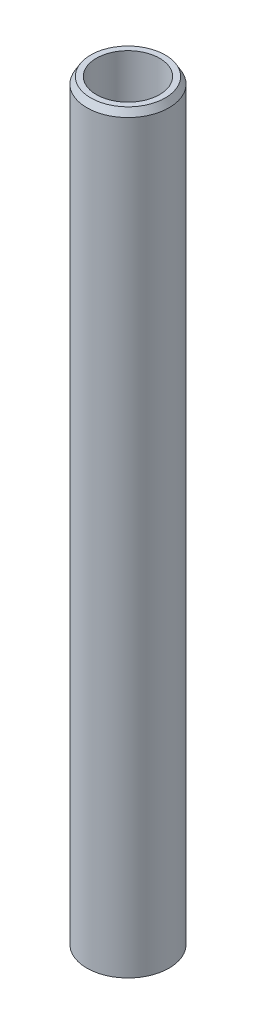
SolidWorks part; units mm, degrees
ref_plane "Front Plane" through (0, 0, 0) normal (0, 0, 1) x (1, 0, 0)
ref_plane "Top Plane" through (0, 0, 0) normal (0, 1, 0) x (1, 0, 0)
ref_plane "Right Plane" through (0, 0, 0) normal (1, 0, 0) x (0, 0, -1)
sketch "Sketch1" plane through (0, 0, 0) normal (0, 1, 0) x (1, 0, 0)
  circle A0 centre (0, 0) radius 17.5
  dimension "SHAFT_OD" = 35
extrude "Boss-Extrude1" add sketch "Sketch1" along normal blind 321.8855
sketch "Sketch2" plane through (0, 0, 0) normal (0, 1, 0) x (1, 0, 0)
  circle A0 centre (0, 0) radius 13.4564
  dimension "BORE_D" = 26.9128
extrude "Cut-Extrude1" cut sketch "Sketch2" along normal through all
chamfer "Chamfer1" distance 2.8177 angle 30 2 edges at (0, 321.8855, 17.5) (0, 0, 17.5) first distance on face at (0, 321.8855, 17.5) first distance on face at (0, 0, 13.4564)
